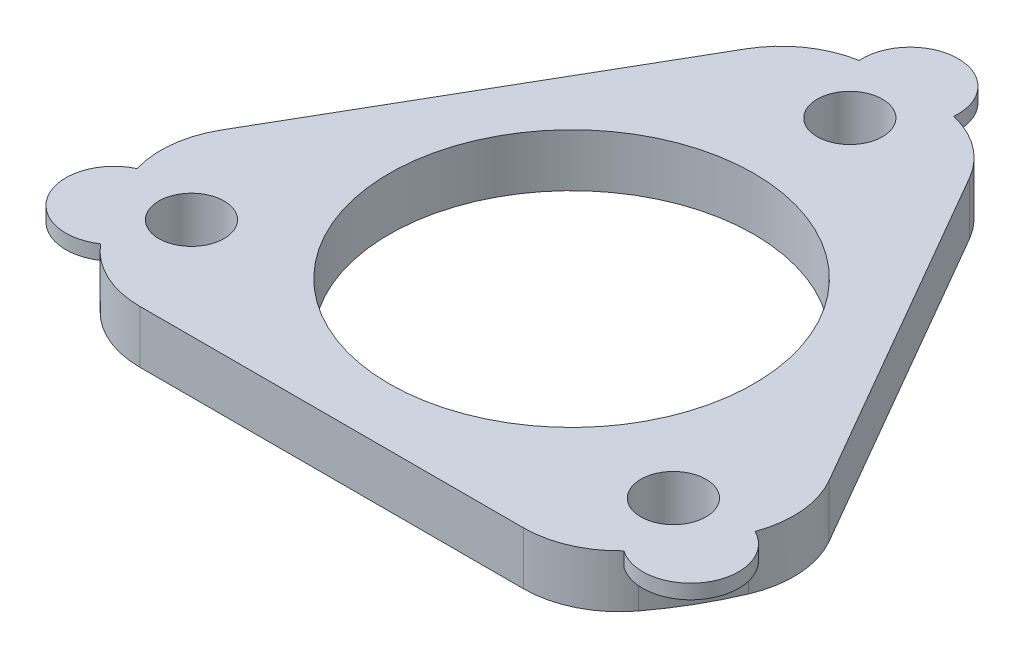
SolidWorks part; units mm, degrees
ref_plane "Спереди" through (0, 0, 0) normal (0, 0, 1) x (1, 0, 0)
ref_plane "Сверху" through (0, 0, 0) normal (0, 1, 0) x (1, 0, 0)
ref_plane "Справа" through (0, 0, 0) normal (1, 0, 0) x (0, 0, -1)
sketch "Sketch1" plane through (0, 0, 0) normal (0, 1, 0) x (1, 0, 0)
  circle A0 centre (0, 0) radius 17.5
  dimension "D1" = 35
extrude "Boss-Extrude1" add sketch "Sketch1" along normal blind 5.5
sketch "Sketch2" plane through (0, 0, 0) normal (0, 1, 0) x (1, 0, 0)
  circle A0 centre (0, 0) radius 35
  circle A1 centre (0, 0) radius 17.5
  circle A2 centre (0, 0) radius 29 construction
  circle A3 centre (0, 29) radius 2.8
  circle A4 centre (25.1147, -14.5) radius 2.8
  circle A5 centre (-25.1147, -14.5) radius 2.8
  point P16 (0, 0)
  dimension "D2" = 58
  dimension "D3" = 35
  dimension "D4" = 70
  dimension "D1" = 3
extrude "Boss-Extrude2" add sketch "Sketch2" along normal blind 5.5
sketch "Sketch4" plane through (0, 0, 0) normal (0, -1, 0) x (1, 0, 0)
  circle A0 centre (-25.1147, 14.5) radius 2.9
  circle A1 centre (25.1147, 14.5) radius 2.9
  circle A2 centre (0, -29) radius 2.9
  point P9 (0, 0)
  dimension "D1" = 3
extrude "Boss-Extrude3" add sketch "Sketch4" along normal blind 2 and the other way up to surface (5.5 mm away) other way up to face at (25.1147, 5.5, 17.3)
sketch "Sketch5" plane through (0, 5.5, 0) normal (0, 1, 0) x (1, 0, 0)
  circle A0 centre (-30.4536, -17.2504) radius 5
  circle A1 centre (0, 0) radius 35 construction
  circle A2 centre (0.2875, 34.9988) radius 5
  circle A3 centre (30.1661, -17.7484) radius 5
  point P10 (0, 0)
  dimension "D1" = 3
extrude "Boss-Extrude4" add sketch "Sketch5" against normal blind 1.5
sketch "Sketch3" plane through (0, 5.5, 0) normal (0, 1, 0) x (1, 0, 0)
  circle A0 centre (0, 0) radius 17.5
  dimension "D1" = 35
extrude "Cut-Extrude1" cut sketch "Sketch3" against normal blind 10
sketch "Sketch12" plane through (0, 5.5, 0) normal (0, 1, 0) x (1, 0, 0)
  line L1 (0, 50) -> (-43.3013, -25)
  line L2 (-43.3013, -25) -> (43.3013, -25)
  line L3 (43.3013, -25) -> (0, 50)
  circle A0 centre (0, 0) radius 25 construction
  circle A1 centre (0, 0) radius 72.1359
extrude "Cut-Extrude2" cut sketch "Sketch12" against normal blind 22
fillet "Fillet1" radius 10 6 edges at (-24.4949, 2.75, 25) (-33.8981, 2.75, 8.7132) (24.4949, 2.75, 25) (33.8981, 2.75, 8.7132) (9.4032, 2.75, -33.7132) (-9.4032, 2.75, -33.7132)
sketch "Sketch13" plane through (0, 5.5, 0) normal (0, 1, 0) x (1, 0, 0)
  circle A0 centre (0, 29) radius 3.4
  circle A1 centre (25.1147, -14.5) radius 3.4
  circle A2 centre (-25.1147, -14.5) radius 3.4
extrude "Cut-Extrude3" cut sketch "Sketch13" against normal blind 10
sketch "Sketch14" plane through (0, 5.5, 0) normal (0, 1, 0) x (1, 0, 0)
  circle A0 centre (0, 0) radius 19
extrude "Cut-Extrude4" cut sketch "Sketch14" against normal blind 10
